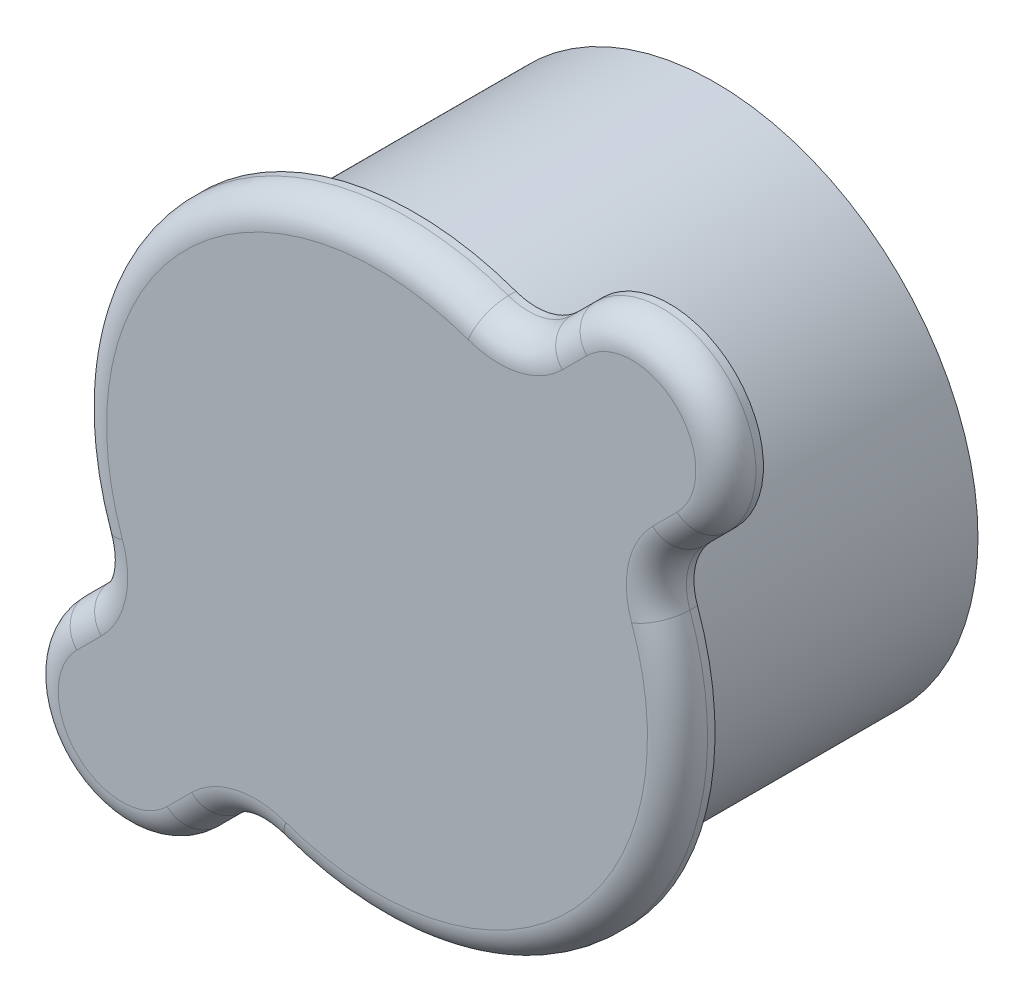
SolidWorks part; units mm, degrees
material "Chrome Stainless Steel"
ref_plane "Front Plane" through (0, 0, 0) normal (0, 0, 1) x (1, 0, 0)
ref_plane "Top Plane" through (0, 0, 0) normal (0, 1, 0) x (1, 0, 0)
ref_plane "Right Plane" through (0, 0, 0) normal (1, 0, 0) x (0, 0, -1)
sketch "Sketch1" plane through (0, 0, 0) normal (0, 0, 1) x (1, 0, 0)
  line L4 (15.94, 27.1653) -> (13.8755, 25.1008)
  line L5 (-25.1008, -13.8755) -> (-27.1653, -15.94)
  line L6 (-15.94, -27.1653) -> (-13.8755, -25.1008)
  line L7 (25.1008, 13.8755) -> (27.1653, 15.94)
  line L8 (15.94, 27.1653) -> (13.8755, 25.1008)
  line L9 (-25.1008, -13.8755) -> (-27.1653, -15.94)
  line L10 (-15.94, -27.1653) -> (-13.8755, -25.1008)
  line L11 (25.1008, 13.8755) -> (27.1653, 15.94)
  circle A0 centre (0, 0) radius 22.225 construction
  circle A1 centre (0, 0) radius 22.225
  arc A8 (8.5695, 23.9108) -> (13.8755, 25.1008) centre (10.2834, 28.6929) ccw
  arc A9 (8.5695, 23.9108) -> (-23.9108, -8.5695) centre (0, 0) ccw
  arc A10 (-25.1008, -13.8755) -> (-23.9108, -8.5695) centre (-28.6929, -10.2834) ccw
  arc A11 (-27.1653, -15.94) -> (-15.94, -27.1653) centre (-21.5526, -21.5526) ccw
  arc A12 (-8.5695, -23.9108) -> (-13.8755, -25.1008) centre (-10.2834, -28.6929) ccw
  arc A13 (-8.5695, -23.9108) -> (23.9108, 8.5695) centre (0, 0) ccw
  arc A14 (25.1008, 13.8755) -> (23.9108, 8.5695) centre (28.6929, 10.2834) ccw
  arc A15 (27.1653, 15.94) -> (15.94, 27.1653) centre (21.5526, 21.5526) ccw
  arc A16 (8.5695, 23.9108) -> (13.8755, 25.1008) centre (10.2834, 28.6929) ccw
  arc A17 (8.5695, 23.9108) -> (-23.9108, -8.5695) centre (0, 0) ccw
  arc A18 (-25.1008, -13.8755) -> (-23.9108, -8.5695) centre (-28.6929, -10.2834) ccw
  arc A19 (-27.1653, -15.94) -> (-15.94, -27.1653) centre (-21.5526, -21.5526) ccw
  arc A20 (-8.5695, -23.9108) -> (-13.8755, -25.1008) centre (-10.2834, -28.6929) ccw
  arc A21 (-8.5695, -23.9108) -> (23.9108, 8.5695) centre (0, 0) ccw
  arc A22 (25.1008, 13.8755) -> (23.9108, 8.5695) centre (28.6929, 10.2834) ccw
  arc A23 (27.1653, 15.94) -> (15.94, 27.1653) centre (21.5526, 21.5526) ccw
  dimension "D1" = 0
extrude "Boss-Extrude1" add sketch "Sketch1" along normal blind 3.175 contours A1 | L11 A23 L8 A16 A17 A18 L9 A19 L10 A20 A21 A22 A1 region at (26.5755, 26.5755, 0) region at (0, 0, 0)
fillet "Fillet1" radius 2.54 12 edges at (23.736, 11.3951, 3.175) (17.9605, -17.9605, 3.175) (-11.3951, -23.736, 3.175) (-14.9077, -26.133, 3.175) (-27.1653, -27.1653, 3.175) (-26.133, -14.9077, 3.175) (-23.736, -11.3951, 3.175) (-17.9605, 17.9605, 3.175) (11.3951, 23.736, 3.175) (14.9077, 26.133, 3.175) (27.1653, 27.1653, 3.175) (26.133, 14.9077, 3.175)
extrude "Boss-Extrude2" add sketch "Sketch1<3>" against normal blind 25.4 contours A1 region at (0, 0, 0)
sketch "Sketch1<3>" plane through (0, 0, 0) normal (0, 0, 1) x (1, 0, 0) same geometry as "Sketch1"
